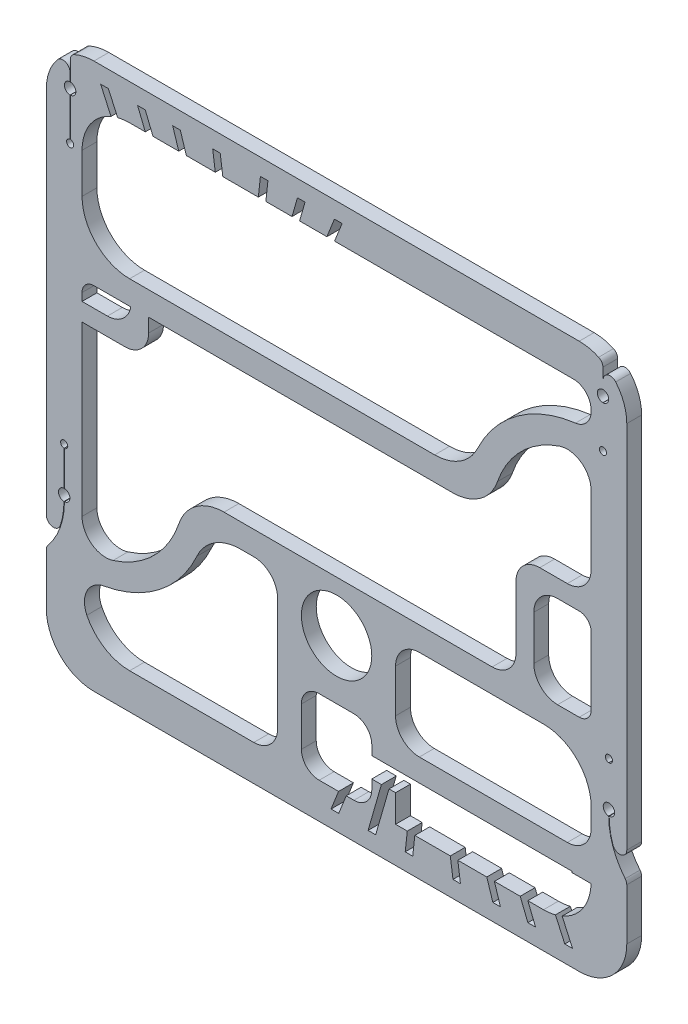
SolidWorks part; units mm, degrees
ref_plane "Front Plane" through (0, 0, 0) normal (0, 0, 1) x (1, 0, 0)
ref_plane "Top Plane" through (0, 0, 0) normal (0, 1, 0) x (1, 0, 0)
ref_plane "Right Plane" through (0, 0, 0) normal (1, 0, 0) x (0, 0, -1)
sketch "Sketch1" plane through (0, 0, 0) normal (0, 0, 1) x (1, 0, 0)
  line L0 (44.642, 21.8842) -> (44.642, 18.0742) construction
  line L1 (-10.1934, 21.8842) -> (51.7832, 21.8842)
  line L2 (-10.1934, 21.8842) -> (-10.1934, -36.406)
  line L3 (-10.1934, -36.406) -> (51.7832, -36.406)
  line L4 (51.7832, 21.8842) -> (51.7832, -36.406)
  line L5 (47.9732, -32.596) -> (-6.3834, -32.596)
  line L6 (47.9732, -32.596) -> (47.9732, 18.0742)
  line L7 (47.9732, 18.0742) -> (-6.3834, 18.0742)
  line L8 (-6.3834, -32.596) -> (-6.3834, 18.0742)
  line L9 (44.642, 19.9792) -> (-35.1587, 19.9792) construction
  line L10 (-6.3834, -31.0517) -> (-10.1934, -31.0517) construction
  line L11 (-8.2884, -31.0517) -> (-8.2884, 6.9585) construction
  line L12 (20.6521, 19.9792) -> (21.1982, 19.9792) construction
  line L14 (3.0779, -32.596) -> (3.0779, -36.406) construction
  line L15 (3.0779, -34.501) -> (37.3423, -34.501) construction
  line L16 (47.9732, -11.8991) -> (47.9732, 12.9942) construction
  line L17 (51.7832, 15.2205) -> (47.9732, 15.2205) construction
  line L18 (49.8782, 15.2205) -> (49.8782, -0.9437) construction
  line L20 (20.9378, -34.501) -> (20.3916, -34.501) construction
  line L21 (-6.3834, 8.0412) -> (-6.3834, -11.8991) construction
  dimension "D1" = 3.81
  dimension "D2" = 3.81
extrude "Boss-Extrude1" add sketch "Sketch1" along normal blind 1.5875
sketch "Sketch2" plane through (0, 0, 0) normal (0, 0, -1) x (-1, 0, 0)
  line L0 (-47.9732, -32.596) -> (-47.9732, 18.0742) construction
  line L1 (-34.8696, 3.653) -> (6.3834, 3.653)
  line L2 (-47.9732, 3.653) -> (-47.9732, 0.8076)
  line L3 (-37.4096, 1.113) -> (6.3834, 1.113)
  line L4 (6.3834, 3.653) -> (6.3834, 1.113)
  line L5 (6.3834, 18.0742) -> (6.3834, -32.596) construction
  line L6 (-33.4496, 1.113) -> (-36.4496, 1.113) construction
  line L7 (1.2504, -12.887) -> (-36.4496, -12.887) construction
  line L8 (-47.9732, -15.427) -> (-6.8239, -15.427)
  line L9 (-47.9732, -15.427) -> (-47.9732, -12.887)
  line L10 (-47.9732, -12.887) -> (-4.5259, -12.887)
  line L11 (1.357, -21.2563) -> (14.2432, -21.2563) construction
  line L12 (6.3834, -23.7963) -> (6.3834, -26.3363)
  line L13 (-47.9732, 14.2166) -> (-47.9732, 11.6766)
  arc A0 (-47.9732, 11.6766) -> (-37.4096, 1.113) centre (-47.9732, 1.113) cw
  arc A1 (-47.9732, 14.2166) -> (-34.8696, 3.653) centre (-47.9732, 0.8076) cw
  arc A2 (6.3834, -23.7963) -> (-4.5259, -12.887) centre (6.3834, -12.887) cw
  arc A3 (-6.8239, -15.427) -> (6.3834, -26.3363) centre (6.3834, -12.887) ccw
  circle A5 centre (1.357, -18.2591) radius 2.9972 construction
  line M5 (-47.9732, -32.596) -> (-47.9732, 18.0742)
  line M7 (6.3834, 18.0742) -> (6.3834, -32.596)
  dimension "D5" = 2.54
  dimension "D1" = 2.54
  dimension "D2" = 2.54
  dimension "D3" = 2.54
  dimension "D4" = 2.54
  dimension "D6" = 2.54
  dimension "D7" = 2.54
extrude "Boss-Extrude2" add sketch "Sketch2" against normal up to surface (1.5875 mm away) contours A1 A0 L3 L1 M5 M7 | L10 L8 M5 M7 region at (14.2431, 3.0939, 0) region at (-5.8234, -25.0663, 0) up to face at (20.7949, -7.2609, 1.5875)
sketch "Sketch3" plane through (0, 0, 0) normal (0, 0, -1) x (-1, 0, 0)
  line L0 (-47.9732, -1.1649) -> (-39.9496, -1.1649)
  line L1 (-47.9732, -12.887) -> (-47.9732, 11.6766) construction
  line L2 (-39.9496, -4.387) -> (-39.9496, -11.387) construction
  line L3 (-39.9496, -1.1649) -> (-39.9496, -12.887)
  line L4 (-47.9732, -12.887) -> (-4.5259, -12.887) construction
  line L5 (-39.9496, -12.887) -> (-41.8546, -12.887)
  line L6 (-41.8546, -12.887) -> (-41.8546, -3.0699)
  line L7 (-41.8546, -3.0699) -> (-47.9732, -3.0699)
  line L8 (-47.9732, -3.0699) -> (-47.9732, -1.1649)
  line L9 (-42.9468, 0.7401) -> (-53.4831, 0.7401) construction
  line L10 (-0.7296, 1.113) -> (-0.7296, -2.887)
  line L11 (-37.4096, 1.113) -> (6.3834, 1.113) construction
  line L12 (-1.9996, -2.887) -> (1.2504, -2.887) construction
  line L13 (-0.7296, -2.887) -> (6.3834, -2.887)
  line L14 (6.3834, 1.113) -> (6.3834, -23.7963) construction
  line L15 (6.3834, -2.887) -> (6.3834, -0.982)
  line L16 (6.3834, -0.982) -> (1.1754, -0.982)
  line L17 (1.1754, -0.982) -> (1.1754, 1.113)
  line L18 (1.1754, 1.113) -> (-0.7296, 1.113)
  circle A0 centre (-42.9468, 3.7373) radius 2.9972 construction
  dimension "D1" = 1.905
  dimension "D2" = 1.905
  dimension "D3" = 1.905
  dimension "D4" = 1.905
  dimension "D5" = 1.27
  dimension "D6" = 1.905
extrude "Boss-Extrude3" add sketch "Sketch3" against normal up to surface (1.5875 mm away) up to face at (20.8645, -5.9566, 1.5875)
fillet "Fillet1" radius 5.08 4 edges at (51.7832, -36.406, 0.7937) (-10.1934, -36.406, 0.7937) (-10.1934, 21.8842, 0.7937) (51.7832, 21.8842, 0.7937)
fillet "Fillet2" radius 5.08 9 edges at (6.8239, -15.427, 0.7937) (47.9732, -15.427, 0.7937) (47.9732, -32.596, 0.7937) (-6.3834, -32.596, 0.7937) (34.8696, 3.653, 0.7938) (-6.3834, 3.653, 0.7937) (-6.3834, 18.0742, 0.7937) (4.5259, -12.887, 0.7937) (37.4096, 1.113, 0.7938)
fillet "Fillet3" radius 2.54 10 edges at (41.8546, -3.0699, 0.7938) (39.9496, -12.887, 0.7938) (41.8546, -12.887, 0.7938) (39.9496, -1.1649, 0.7938) (47.9732, -1.1649, 0.7938) (-1.1754, -0.982, 0.7938) (0.7296, -2.887, 0.7938) (47.9732, 11.6766, 0.7937) (-6.3834, -26.3363, 0.7937) (-6.3834, -23.7963, 0.7937)
fillet "Fillet4" radius 1.27 3 edges at (47.9732, -12.887, 0.7937) (47.9732, -3.0699, 0.7938) (-6.3834, 1.113, 0.7938)
sketch "Sketch5" plane through (0, 0, 0) normal (0, 0, -1) x (-1, 0, 0)
  line L0 (-42.8932, -15.427) -> (-10.5066, -15.427) construction
  line L1 (-27.0941, -15.427) -> (-14.4957, -15.427)
  line L2 (-27.0941, -15.427) -> (-27.0941, -32.596)
  line L3 (-27.0941, -32.596) -> (-14.4957, -32.596)
  line L4 (-14.4957, -15.427) -> (-14.4957, -32.596)
  line L5 (1.3034, -32.596) -> (-42.8932, -32.596) construction
  line L6 (-24.5541, -18.2972) -> (-27.0941, -18.2972) construction
  line L9 (-17.0357, -18.2972) -> (-14.4957, -18.2972) construction
  circle A1 centre (-20.7949, -18.2972) radius 3.7592 construction
  dimension "D1" = 2.54
extrude "Boss-Extrude4" add sketch "Sketch5" against normal up to surface (1.5875 mm away) up to face at (-4.5227, -0.0173, 1.5875)
sketch "Sketch6" plane through (0, 0, 0) normal (0, 0, -1) x (-1, 0, 0)
  circle A0 centre (-20.7949, -18.2972) radius 3.7592 construction
  circle A1 centre (-20.7949, -18.2972) radius 3.7592
extrude "Cut-Extrude2" cut sketch "Sketch6" against normal up to surface (1.5875 mm away) up to face at (4.768, -24.4396, 1.5875)
sketch "Sketch7" plane through (0, 0, 0) normal (0, 0, -1) x (-1, 0, 0)
  line L0 (-27.0941, -15.427) -> (-27.0941, -32.596) construction
  line L1 (-24.5541, -24.5964) -> (-17.0357, -24.5964)
  line L2 (-24.5541, -24.5964) -> (-24.5541, -32.596)
  line L3 (-24.5541, -32.596) -> (-17.0357, -32.596)
  line L4 (-17.0357, -24.5964) -> (-17.0357, -32.596)
  line L5 (-14.4957, -32.596) -> (-14.4957, -15.427) construction
  line L6 (1.3034, -32.596) -> (-14.4957, -32.596) construction
  line L7 (-20.7949, -22.0564) -> (-6.5424, -22.0564) construction
  line L8 (-20.7949, -22.0564) -> (-20.7949, -21.3452) construction
  circle A0 centre (-20.7949, -18.2972) radius 3.7592 construction
  dimension "D1" = 2.54
  dimension "D2" = 2.54
  dimension "D3" = 2.54
extrude "Cut-Extrude3" cut sketch "Sketch7" against normal up to surface (1.5875 mm away) up to face at (24.5541, -18.2972, 1.5875)
fillet "Fillet5" radius 1.905 4 edges at (24.5541, -32.596, 0.7937) (17.0357, -32.596, 0.7938) (17.0357, -24.5964, 0.7938) (24.5541, -24.5964, 0.7938)
sketch "Sketch8" plane through (0, 0, 0) normal (0, 0, -1) x (-1, 0, 0)
  line L0 (-47.9732, -27.516) -> (-47.9732, -20.507) construction
  line L1 (-47.9732, -25.103) -> (-27.0941, -25.103)
  line L2 (-47.9732, -25.103) -> (-47.9732, -27.643)
  line L3 (-47.9732, -27.643) -> (-27.0941, -27.643)
  line L4 (-27.0941, -25.103) -> (-27.0941, -27.643)
  line L5 (-27.0941, -15.427) -> (-27.0941, -32.596) construction
  line L6 (-45.7916, -27.643) -> (-20.3916, -27.643) construction
  dimension "D1" = 2.54
extrude "Boss-Extrude5" add sketch "Sketch8" against normal up to surface (1.5875 mm away) up to face at (20.7949, -28.5962, 1.5875)
fillet "Fillet6" radius 2.54 5 edges at (27.0941, -15.427, 0.7937) (14.4957, -15.427, 0.7937) (14.4957, -32.596, 0.7937) (27.0941, -25.103, 0.7937) (47.9732, -25.103, 0.7937)
sketch "Sketch4" plane through (0, 0, 0) normal (0, 0, -1) x (-1, 0, 0)
  line L0 (3.2504, -2.887) -> (4.7504, -4.387) construction
  line L1 (4.7504, -11.387) -> (3.2504, -12.887) construction
  line L2 (3.2504, -2.887) -> (4.7504, -4.387)
  line L3 (4.7504, -11.387) -> (3.2504, -12.887)
  line L4 (4.7504, -4.387) -> (4.7504, -11.387) construction
  line L5 (4.7504, -4.387) -> (4.7504, -11.387)
  line L6 (3.2504, -2.887) -> (3.2504, -12.887)
  line L32 (4.2018, 13.1212) -> (4.2018, 15.0262)
  line L33 (4.2018, 15.0262) -> (1.9539, 15.0262)
  line L34 (1.9539, 15.0262) -> (4.2018, 19.9792)
  line L35 (4.2018, 19.9792) -> (3.6556, 19.9792)
  line L36 (3.6556, 19.9792) -> (1.4078, 15.0262)
  line L37 (1.4078, 15.0262) -> (-1.7417, 15.0262)
  line L38 (-1.7417, 15.0262) -> (0.2648, 19.9792)
  line L39 (0.2648, 19.9792) -> (-0.2814, 19.9792)
  line L40 (-0.2814, 19.9792) -> (-2.2879, 15.0262)
  line L41 (-2.2879, 15.0262) -> (-5.0437, 15.0262)
  line L42 (-5.0437, 15.0262) -> (-3.469, 19.9792)
  line L43 (-3.469, 19.9792) -> (-4.0152, 19.9792)
  line L44 (-4.0152, 19.9792) -> (-5.5899, 15.0262)
  line L45 (-5.5899, 15.0262) -> (-8.3965, 15.0262)
  line L46 (-8.3965, 15.0262) -> (-7.7108, 19.9792)
  line L47 (-7.7108, 19.9792) -> (-8.257, 19.9792)
  line L48 (-8.257, 19.9792) -> (-8.9427, 15.0262)
  line L49 (-8.9427, 15.0262) -> (-12.2319, 15.0262)
  line L50 (-12.2319, 15.0262) -> (-12.7781, 19.9792)
  line L51 (-12.7781, 19.9792) -> (-13.3242, 19.9792)
  line L52 (-13.3242, 19.9792) -> (-12.7781, 15.0262)
  line L53 (-12.7781, 15.0262) -> (-15.2926, 15.0262)
  line L54 (-15.2926, 15.0262) -> (-16.7151, 19.9792)
  line L55 (-16.7151, 19.9792) -> (-17.2612, 19.9792)
  line L56 (-17.2612, 19.9792) -> (-15.8388, 15.0262)
  line L57 (-15.8388, 15.0262) -> (-18.6963, 15.0262)
  line L58 (-18.6963, 15.0262) -> (-20.6521, 19.9792)
  line L59 (-20.6521, 19.9792) -> (-21.1982, 19.9792)
  line L60 (-21.1982, 19.9792) -> (-19.2425, 15.0262)
  line L61 (-19.2425, 15.0262) -> (-21.1982, 15.0262)
  line L62 (-21.1982, 15.0262) -> (-21.1982, 13.1212)
  line L63 (-21.1982, 13.1212) -> (4.2018, 13.1212)
  line L64 (4.2018, 13.1212) -> (4.2018, 15.0262) construction
  line L65 (4.2018, 15.0262) -> (1.9539, 15.0262) construction
  line L66 (1.9539, 15.0262) -> (4.2018, 19.9792) construction
  line L67 (4.2018, 19.9792) -> (3.6556, 19.9792) construction
  line L68 (3.6556, 19.9792) -> (1.4078, 15.0262) construction
  line L69 (1.4078, 15.0262) -> (-1.7417, 15.0262) construction
  line L70 (-1.7417, 15.0262) -> (0.2648, 19.9792) construction
  line L71 (0.2648, 19.9792) -> (-0.2814, 19.9792) construction
  line L72 (-0.2814, 19.9792) -> (-2.2879, 15.0262) construction
  line L73 (-2.2879, 15.0262) -> (-5.0437, 15.0262) construction
  line L74 (-5.0437, 15.0262) -> (-3.469, 19.9792) construction
  line L75 (-3.469, 19.9792) -> (-4.0152, 19.9792) construction
  line L76 (-4.0152, 19.9792) -> (-5.5899, 15.0262) construction
  line L77 (-5.5899, 15.0262) -> (-8.3965, 15.0262) construction
  line L78 (-8.3965, 15.0262) -> (-7.7108, 19.9792) construction
  line L79 (-7.7108, 19.9792) -> (-8.257, 19.9792) construction
  line L80 (-8.257, 19.9792) -> (-8.9427, 15.0262) construction
  line L81 (-8.9427, 15.0262) -> (-12.2319, 15.0262) construction
  line L82 (-12.2319, 15.0262) -> (-12.7781, 19.9792) construction
  line L83 (-12.7781, 19.9792) -> (-13.3242, 19.9792) construction
  line L84 (-13.3242, 19.9792) -> (-12.7781, 15.0262) construction
  line L85 (-12.7781, 15.0262) -> (-15.2926, 15.0262) construction
  line L86 (-15.2926, 15.0262) -> (-16.7151, 19.9792) construction
  line L87 (-16.7151, 19.9792) -> (-17.2612, 19.9792) construction
  line L88 (-17.2612, 19.9792) -> (-15.8388, 15.0262) construction
  line L89 (-15.8388, 15.0262) -> (-18.6963, 15.0262) construction
  line L90 (-18.6963, 15.0262) -> (-20.6521, 19.9792) construction
  line L91 (-20.6521, 19.9792) -> (-21.1982, 19.9792) construction
  line L92 (-21.1982, 19.9792) -> (-19.2425, 15.0262) construction
  line L93 (-19.2425, 15.0262) -> (-21.1982, 15.0262) construction
  line L94 (-21.1982, 15.0262) -> (-21.1982, 13.1212) construction
  line L95 (-21.1982, 13.1212) -> (4.2018, 13.1212) construction
  line L96 (-45.7916, -27.643) -> (-45.7916, -29.548)
  line L97 (-45.7916, -29.548) -> (-43.5438, -29.548)
  line L98 (-43.5438, -29.548) -> (-45.7916, -34.501)
  line L99 (-45.7916, -34.501) -> (-45.2455, -34.501)
  line L100 (-45.2455, -34.501) -> (-42.9976, -29.548)
  line L101 (-42.9976, -29.548) -> (-39.8482, -29.548)
  line L102 (-39.8482, -29.548) -> (-41.8546, -34.501)
  line L103 (-41.8546, -34.501) -> (-41.3085, -34.501)
  line L104 (-41.3085, -34.501) -> (-39.302, -29.548)
  line L105 (-39.302, -29.548) -> (-36.5462, -29.548)
  line L106 (-36.5462, -29.548) -> (-38.1208, -34.501)
  line L107 (-38.1208, -34.501) -> (-37.5747, -34.501)
  line L108 (-37.5747, -34.501) -> (-36, -29.548)
  line L109 (-36, -29.548) -> (-33.1934, -29.548)
  line L110 (-33.1934, -29.548) -> (-33.879, -34.501)
  line L111 (-33.879, -34.501) -> (-33.3329, -34.501)
  line L112 (-33.3329, -34.501) -> (-32.6472, -29.548)
  line L113 (-32.6472, -29.548) -> (-29.358, -29.548)
  line L114 (-29.358, -29.548) -> (-28.8118, -34.501)
  line L115 (-28.8118, -34.501) -> (-28.2656, -34.501)
  line L116 (-28.2656, -34.501) -> (-28.8118, -29.548)
  line L117 (-28.8118, -29.548) -> (-26.2973, -29.548)
  line L118 (-26.2973, -29.548) -> (-24.8748, -34.501)
  line L119 (-24.8748, -34.501) -> (-24.3286, -34.501)
  line L120 (-24.3286, -34.501) -> (-25.7511, -29.548)
  line L121 (-25.7511, -29.548) -> (-22.8935, -29.548)
  line L122 (-22.8935, -29.548) -> (-20.9378, -34.501)
  line L123 (-20.9378, -34.501) -> (-20.3916, -34.501)
  line L124 (-20.3916, -34.501) -> (-22.3474, -29.548)
  line L125 (-22.3474, -29.548) -> (-20.3916, -29.548)
  line L126 (-20.3916, -29.548) -> (-20.3916, -27.643)
  line L127 (-20.3916, -27.643) -> (-45.7916, -27.643)
  line L128 (-45.7916, -27.643) -> (-45.7916, -29.548) construction
  line L129 (-45.7916, -29.548) -> (-43.5438, -29.548) construction
  line L130 (-43.5438, -29.548) -> (-45.7916, -34.501) construction
  line L131 (-45.7916, -34.501) -> (-45.2455, -34.501) construction
  line L132 (-45.2455, -34.501) -> (-42.9976, -29.548) construction
  line L133 (-42.9976, -29.548) -> (-39.8482, -29.548) construction
  line L134 (-39.8482, -29.548) -> (-41.8546, -34.501) construction
  line L135 (-41.8546, -34.501) -> (-41.3085, -34.501) construction
  line L136 (-41.3085, -34.501) -> (-39.302, -29.548) construction
  line L137 (-39.302, -29.548) -> (-36.5462, -29.548) construction
  line L138 (-36.5462, -29.548) -> (-38.1208, -34.501) construction
  line L139 (-38.1208, -34.501) -> (-37.5747, -34.501) construction
  line L140 (-37.5747, -34.501) -> (-36, -29.548) construction
  line L141 (-36, -29.548) -> (-33.1934, -29.548) construction
  line L142 (-33.1934, -29.548) -> (-33.879, -34.501) construction
  line L143 (-33.879, -34.501) -> (-33.3329, -34.501) construction
  line L144 (-33.3329, -34.501) -> (-32.6472, -29.548) construction
  line L145 (-32.6472, -29.548) -> (-29.358, -29.548) construction
  line L146 (-29.358, -29.548) -> (-28.8118, -34.501) construction
  line L147 (-28.8118, -34.501) -> (-28.2656, -34.501) construction
  line L148 (-28.2656, -34.501) -> (-28.8118, -29.548) construction
  line L149 (-28.8118, -29.548) -> (-26.2973, -29.548) construction
  line L150 (-26.2973, -29.548) -> (-24.8748, -34.501) construction
  line L151 (-24.8748, -34.501) -> (-24.3286, -34.501) construction
  line L152 (-24.3286, -34.501) -> (-25.7511, -29.548) construction
  line L153 (-25.7511, -29.548) -> (-22.8935, -29.548) construction
  line L154 (-22.8935, -29.548) -> (-20.9378, -34.501) construction
  line L155 (-20.9378, -34.501) -> (-20.3916, -34.501) construction
  line L156 (-20.3916, -34.501) -> (-22.3474, -29.548) construction
  line L157 (-22.3474, -29.548) -> (-20.3916, -29.548) construction
  line L158 (-20.3916, -29.548) -> (-20.3916, -27.643) construction
  line L159 (-20.3916, -27.643) -> (-45.7916, -27.643) construction
  line L263 (4.3288, 12.9942) -> (4.3288, 15.1532)
  line L264 (4.3288, 15.1532) -> (2.151, 15.1532)
  line L265 (2.151, 15.1532) -> (4.3989, 20.1062)
  line L266 (4.3989, 20.1062) -> (3.5738, 20.1062)
  line L267 (3.5738, 20.1062) -> (1.3259, 15.1532)
  line L268 (1.3259, 15.1532) -> (-1.5532, 15.1532)
  line L269 (-1.5532, 15.1532) -> (0.4532, 20.1062)
  line L270 (0.4532, 20.1062) -> (-0.367, 20.1062)
  line L271 (-0.367, 20.1062) -> (-2.3735, 15.1532)
  line L272 (-2.3735, 15.1532) -> (-4.8701, 15.1532)
  line L273 (-4.8701, 15.1532) -> (-3.2954, 20.1062)
  line L274 (-3.2954, 20.1062) -> (-4.1081, 20.1062)
  line L275 (-4.1081, 20.1062) -> (-5.6828, 15.1532)
  line L276 (-5.6828, 15.1532) -> (-8.2507, 15.1532)
  line L277 (-8.2507, 15.1532) -> (-7.565, 20.1062)
  line L278 (-7.565, 20.1062) -> (-8.3676, 20.1062)
  line L279 (-8.3676, 20.1062) -> (-9.0533, 15.1532)
  line L280 (-9.0533, 15.1532) -> (-12.1181, 15.1532)
  line L281 (-12.1181, 15.1532) -> (-12.6643, 20.1062)
  line L282 (-12.6643, 20.1062) -> (-13.466, 20.1062)
  line L283 (-13.466, 20.1062) -> (-12.9198, 15.1532)
  line L284 (-12.9198, 15.1532) -> (-15.1969, 15.1532)
  line L285 (-15.1969, 15.1532) -> (-16.6194, 20.1062)
  line L286 (-16.6194, 20.1062) -> (-17.4298, 20.1062)
  line L287 (-17.4298, 20.1062) -> (-16.0074, 15.1532)
  line L288 (-16.0074, 15.1532) -> (-18.6099, 15.1532)
  line L289 (-18.6099, 15.1532) -> (-20.5657, 20.1062)
  line L290 (-20.5657, 20.1062) -> (-21.3849, 20.1062)
  line L291 (-21.3849, 20.1062) -> (-19.4292, 15.1532)
  line L292 (-19.4292, 15.1532) -> (-21.3252, 15.1532)
  line L293 (-21.3252, 15.1532) -> (-21.3252, 12.9942)
  line L294 (-21.3252, 12.9942) -> (4.3288, 12.9942)
  line L295 (-45.9186, -27.516) -> (-45.9186, -29.675)
  line L296 (-45.9186, -29.675) -> (-43.7409, -29.675)
  line L297 (-43.7409, -29.675) -> (-45.9887, -34.628)
  line L298 (-45.9887, -34.628) -> (-45.1636, -34.628)
  line L299 (-45.1636, -34.628) -> (-42.9158, -29.675)
  line L300 (-42.9158, -29.675) -> (-40.0367, -29.675)
  line L301 (-40.0367, -29.675) -> (-42.0431, -34.628)
  line L302 (-42.0431, -34.628) -> (-41.2229, -34.628)
  line L303 (-41.2229, -34.628) -> (-39.2164, -29.675)
  line L304 (-39.2164, -29.675) -> (-36.7198, -29.675)
  line L305 (-36.7198, -29.675) -> (-38.2945, -34.628)
  line L306 (-38.2945, -34.628) -> (-37.4818, -34.628)
  line L307 (-37.4818, -34.628) -> (-35.9071, -29.675)
  line L308 (-35.9071, -29.675) -> (-33.3392, -29.675)
  line L309 (-33.3392, -29.675) -> (-34.0248, -34.628)
  line L310 (-34.0248, -34.628) -> (-33.2222, -34.628)
  line L311 (-33.2222, -34.628) -> (-32.5366, -29.675)
  line L312 (-32.5366, -29.675) -> (-29.4717, -29.675)
  line L313 (-29.4717, -29.675) -> (-28.9256, -34.628)
  line L314 (-28.9256, -34.628) -> (-28.1239, -34.628)
  line L315 (-28.1239, -34.628) -> (-28.67, -29.675)
  line L316 (-28.67, -29.675) -> (-26.3929, -29.675)
  line L317 (-26.3929, -29.675) -> (-24.9705, -34.628)
  line L318 (-24.9705, -34.628) -> (-24.16, -34.628)
  line L319 (-24.16, -34.628) -> (-25.5825, -29.675)
  line L320 (-25.5825, -29.675) -> (-22.9799, -29.675)
  line L321 (-22.9799, -29.675) -> (-21.0242, -34.628)
  line L322 (-21.0242, -34.628) -> (-20.205, -34.628)
  line L323 (-20.205, -34.628) -> (-22.1607, -29.675)
  line L324 (-22.1607, -29.675) -> (-20.2646, -29.675)
  line L325 (-20.2646, -29.675) -> (-20.2646, -27.516)
  line L326 (-20.2646, -27.516) -> (-45.9186, -27.516)
  dimension "D1" = 0
  dimension "D2" = 0
  dimension "D3" = 0.127
  dimension "D4" = 0.127
extrude "Cut-Extrude1" cut sketch "Sketch4" against normal up to surface (1.5875 mm away) up to face at (37.2819, -20.5167, 1.5875)
sketch "Sketch9" plane through (0, 0, 0) normal (0, 0, -1) x (-1, 0, 0)
  circle A0 centre (-49.2432, 18.0742) radius 0.6096 construction
  circle A1 centre (7.6534, 18.0742) radius 0.6096 construction
  circle A2 centre (8.2884, -19.8366) radius 0.6096 construction
  circle A3 centre (-49.8782, -19.8366) radius 0.6096 construction
  circle A4 centre (-49.2432, 18.0742) radius 0.6096
  circle A5 centre (7.6534, 18.0742) radius 0.6096
  circle A6 centre (8.2884, -19.8366) radius 0.6096
  circle A7 centre (-49.8782, -19.8366) radius 0.6096
extrude "Cut-Extrude4" cut sketch "Sketch9" against normal up to surface (1.5875 mm away) up to face at (31.4097, -31.792, 1.5875)
sketch "Sketch10" plane through (0, 0, 1.5875) normal (0, 0, 1) x (1, 0, 0)
  line L0 (-7.6407, 18.6837) -> (-7.6407, 20.7449) construction
  line L1 (-7.6407, 13.375) -> (-7.6407, 17.4647) construction
  line L2 (-7.6661, 17.4647) -> (-7.6661, 13.375) construction
  line L3 (-7.6661, 19.5715) -> (-7.6661, 18.6837) construction
  line L4 (-7.6407, 18.6837) -> (-7.6407, 20.7449)
  line L5 (-7.6407, 13.375) -> (-7.6407, 17.4647)
  line L6 (-7.6661, 17.4647) -> (-7.6661, 13.375)
  line L7 (-7.6661, 19.5715) -> (-7.6661, 18.6837)
  line L8 (49.2305, 18.6837) -> (49.2305, 20.7449) construction
  line L9 (49.2305, 13.375) -> (49.2305, 17.4647) construction
  line L10 (49.2559, 17.4647) -> (49.2559, 13.375) construction
  line L11 (49.2559, 19.5715) -> (49.2559, 18.6837) construction
  line L12 (49.2305, 18.6837) -> (49.2305, 20.7449)
  line L13 (49.2305, 13.375) -> (49.2305, 17.4647)
  line L14 (49.2559, 17.4647) -> (49.2559, 13.375)
  line L15 (49.2559, 19.5715) -> (49.2559, 18.6837)
  line L16 (49.8909, -15.5181) -> (49.8909, -19.2271) construction
  line L17 (49.8655, -15.5181) -> (49.8655, -19.2271) construction
  line L18 (49.8909, -15.5181) -> (49.8909, -19.2271)
  line L19 (49.8655, -15.5181) -> (49.8655, -19.2271)
  line L20 (-8.2757, -15.5181) -> (-8.2757, -19.2271) construction
  line L21 (-8.3011, -15.5181) -> (-8.3011, -19.2271) construction
  line L22 (-8.2757, -15.5181) -> (-8.2757, -19.2271)
  line L23 (-8.3011, -15.5181) -> (-8.3011, -19.2271)
  line L24 (51.7832, -31.326) -> (51.7832, 16.8042) construction
  line L25 (51.7832, -25.8445) -> (51.7832, -22.639)
  line L26 (-10.1934, 16.8042) -> (-10.1934, -31.326) construction
  line L27 (-10.1934, -22.639) -> (-10.1934, -25.8445)
  arc A1 (-7.1902, 21.4403) -> (-7.6407, 20.7449) centre (-6.8787, 20.7449) ccw construction
  arc A2 (-7.6661, 13.375) -> (-7.6407, 13.375) centre (-7.6534, 12.9942) ccw construction
  arc A3 (-7.6661, 19.5715) -> (-9.013, 20.0598) centre (-8.4281, 19.5715) ccw construction
  arc A4 (-5.1134, 21.8842) -> (-10.1934, 16.8042) centre (-5.1134, 16.8042) ccw construction
  arc A5 (-7.1902, 21.4403) -> (-7.6407, 20.7449) centre (-6.8787, 20.7449) ccw
  arc A6 (-7.6661, 13.375) -> (-7.6407, 13.375) centre (-7.6534, 12.9942) ccw
  arc A7 (-7.6661, 19.5715) -> (-9.013, 20.0598) centre (-8.4281, 19.5715) ccw
  arc A8 (-7.1902, 21.4403) -> (-9.013, 20.0598) centre (-5.1134, 16.8042) ccw
  circle A9 centre (-7.6534, 18.0742) radius 0.6096 construction
  arc A10 (-7.6407, 18.6837) -> (-7.6661, 18.6837) centre (-7.6534, 18.0742) ccw
  arc A11 (-7.6661, 17.4647) -> (-7.6407, 17.4647) centre (-7.6534, 18.0742) ccw
  arc A12 (49.2305, 20.7449) -> (48.7801, 21.4403) centre (48.4685, 20.7449) ccw construction
  arc A13 (49.2305, 13.375) -> (49.2559, 13.375) centre (49.2432, 12.9942) ccw construction
  arc A14 (50.6029, 20.0598) -> (49.2559, 19.5715) centre (50.0179, 19.5715) ccw construction
  arc A15 (49.2305, 20.7449) -> (48.7801, 21.4403) centre (48.4685, 20.7449) ccw
  arc A16 (49.2305, 13.375) -> (49.2559, 13.375) centre (49.2432, 12.9942) ccw
  arc A17 (50.6029, 20.0598) -> (49.2559, 19.5715) centre (50.0179, 19.5715) ccw
  arc A18 (49.8909, -15.5181) -> (49.8655, -15.5181) centre (49.8782, -15.1373) ccw construction
  arc A19 (49.9036, -20.4457) -> (50.2983, -22.8798) centre (57.6041, -20.4462) ccw construction
  arc A20 (49.8528, -20.4457) -> (51.6105, -25.3613) centre (57.6041, -20.4462) ccw construction
  arc A21 (50.2983, -22.8798) -> (51.7832, -22.639) centre (51.0212, -22.639) ccw construction
  arc A22 (51.7832, -25.8445) -> (51.6105, -25.3613) centre (51.0212, -25.8445) ccw construction
  arc A23 (49.8909, -15.5181) -> (49.8655, -15.5181) centre (49.8782, -15.1373) ccw
  arc A24 (49.9036, -20.4457) -> (50.2983, -22.8798) centre (57.6041, -20.4462) ccw
  arc A25 (49.8528, -20.4457) -> (51.6105, -25.3613) centre (57.6041, -20.4462) ccw
  arc A26 (50.2983, -22.8798) -> (51.7832, -22.639) centre (51.0212, -22.639) ccw
  arc A27 (51.7832, -25.8445) -> (51.6105, -25.3613) centre (51.0212, -25.8445) ccw
  arc A28 (-10.1934, -22.639) -> (-8.7084, -22.8798) centre (-9.4314, -22.639) ccw construction
  arc A29 (-10.0206, -25.3613) -> (-8.263, -20.4457) centre (-16.0142, -20.4462) ccw construction
  arc A30 (-8.7084, -22.8798) -> (-8.3138, -20.4457) centre (-16.0142, -20.4462) ccw construction
  arc A31 (-8.2757, -15.5181) -> (-8.3011, -15.5181) centre (-8.2884, -15.1373) ccw construction
  arc A32 (-10.1934, -22.639) -> (-8.7084, -22.8798) centre (-9.4314, -22.639) ccw
  arc A33 (-10.0206, -25.3613) -> (-8.263, -20.4457) centre (-16.0142, -20.4462) ccw
  arc A34 (-8.7084, -22.8798) -> (-8.3138, -20.4457) centre (-16.0142, -20.4462) ccw
  arc A35 (-8.2757, -15.5181) -> (-8.3011, -15.5181) centre (-8.2884, -15.1373) ccw
  arc A36 (51.7832, 16.8042) -> (46.7032, 21.8842) centre (46.7032, 16.8042) ccw construction
  arc A37 (50.6029, 20.0598) -> (48.7801, 21.4403) centre (46.7032, 16.8042) ccw
  circle A38 centre (49.2432, 18.0742) radius 0.6096 construction
  arc A39 (49.2559, 18.6837) -> (49.2305, 18.6837) centre (49.2432, 18.0742) ccw
  arc A40 (49.2305, 17.4647) -> (49.2559, 17.4647) centre (49.2432, 18.0742) ccw
  circle A41 centre (49.8782, -19.8366) radius 0.6096 construction
  arc A42 (49.8909, -19.2271) -> (49.8655, -19.2271) centre (49.8782, -19.8366) ccw
  arc A43 (49.8528, -20.4457) -> (49.9036, -20.4457) centre (49.8782, -19.8366) ccw
  circle A44 centre (-8.2884, -19.8366) radius 0.6096 construction
  arc A45 (-8.2757, -19.2271) -> (-8.3011, -19.2271) centre (-8.2884, -19.8366) ccw
  arc A46 (-8.3138, -20.4457) -> (-8.263, -20.4457) centre (-8.2884, -19.8366) ccw
  arc A47 (-10.0206, -25.3613) -> (-10.1934, -25.8445) centre (-9.4314, -25.8445) ccw construction
  arc A48 (-10.0206, -25.3613) -> (-10.1934, -25.8445) centre (-9.4314, -25.8445) ccw
extrude "Slots for carbon" cut sketch "Sketch10" against normal through all
fillet "Fillet7" radius 1.905 2 edges at (47.9732, 14.2166, 0.7937) (47.9732, 18.0742, 0.7937)
